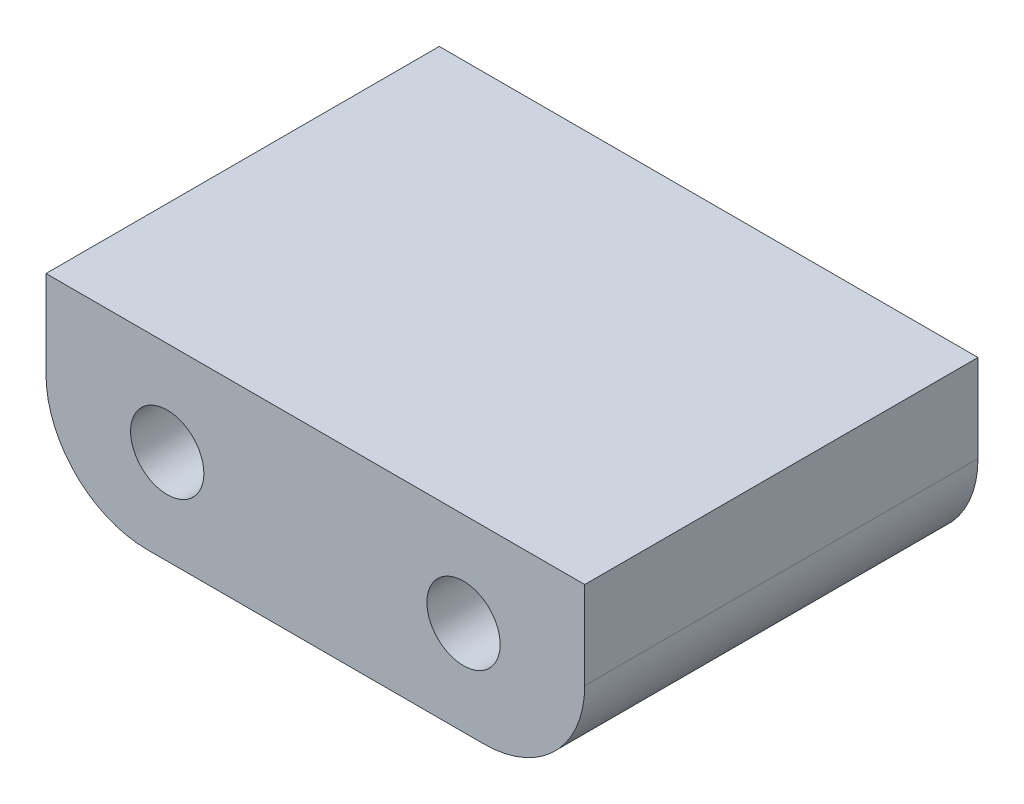
SolidWorks part; units mm, degrees
ref_plane "Front Plane" through (0, 0, 0) normal (0, 0, 1) x (1, 0, 0)
ref_plane "Top Plane" through (0, 0, 0) normal (0, 1, 0) x (1, 0, 0)
ref_plane "Right Plane" through (0, 0, 0) normal (1, 0, 0) x (0, 0, -1)
sketch "Sketch1" plane through (0, 0, 0) normal (0, 1, 0) x (1, 0, 0)
  line L1 (-12.7, 9.271) -> (12.7, 9.271)
  line L2 (-12.7, 9.271) -> (-12.7, -9.271)
  line L3 (-12.7, -9.271) -> (12.7, -9.271)
  line L4 (12.7, 9.271) -> (12.7, -9.271)
  line L5 (-12.7, 9.271) -> (12.7, -9.271) construction
  line L6 (-12.7, -9.271) -> (12.7, 9.271) construction
  point P0 (0, 0)
  dimension "D1" = 25.4
  dimension "D2" = 18.542
extrude "Boss-Extrude1" add sketch "Sketch1" along normal mid plane 8.89
hole_wizard "Tap Drill for #8-32 Tap1" positions "Sketch4" profile "Sketch5" hole size "#8-32" standard "ANSI Inch" end condition through all
sketch "Sketch4" plane through (0, 0, 9.271) normal (0, 0, 1) x (1, 0, 0)
  line L0 (-6.985, 0) -> (6.985, 0)
  point P0 (-6.985, 0)
  point P2 (6.985, 0)
  point P7 (0, 0)
  dimension "D1" = 13.97
sketch "Sketch5" plane through (-6.985, 0, 9.271) normal (1, 0, 0) x (0, -1, 0)
  line L0 (0, 0) -> (0, 18.542)
  line L1 (0, 18.542) -> (1.7272, 18.542)
  line L2 (1.7272, 18.542) -> (1.7272, 0)
  line L5 (1.7272, 0) -> (0, 0)
  line L11 (0, -6.35) -> (0, 107.95) construction
  dimension "Thru Hole Dia." = 3.4544
  dimension "Thru Hole Depth" = 18.542
fillet "Fillet1" radius 4.7625 2 edges at (12.7, -4.445, 0) (-12.7, -4.445, 0)
